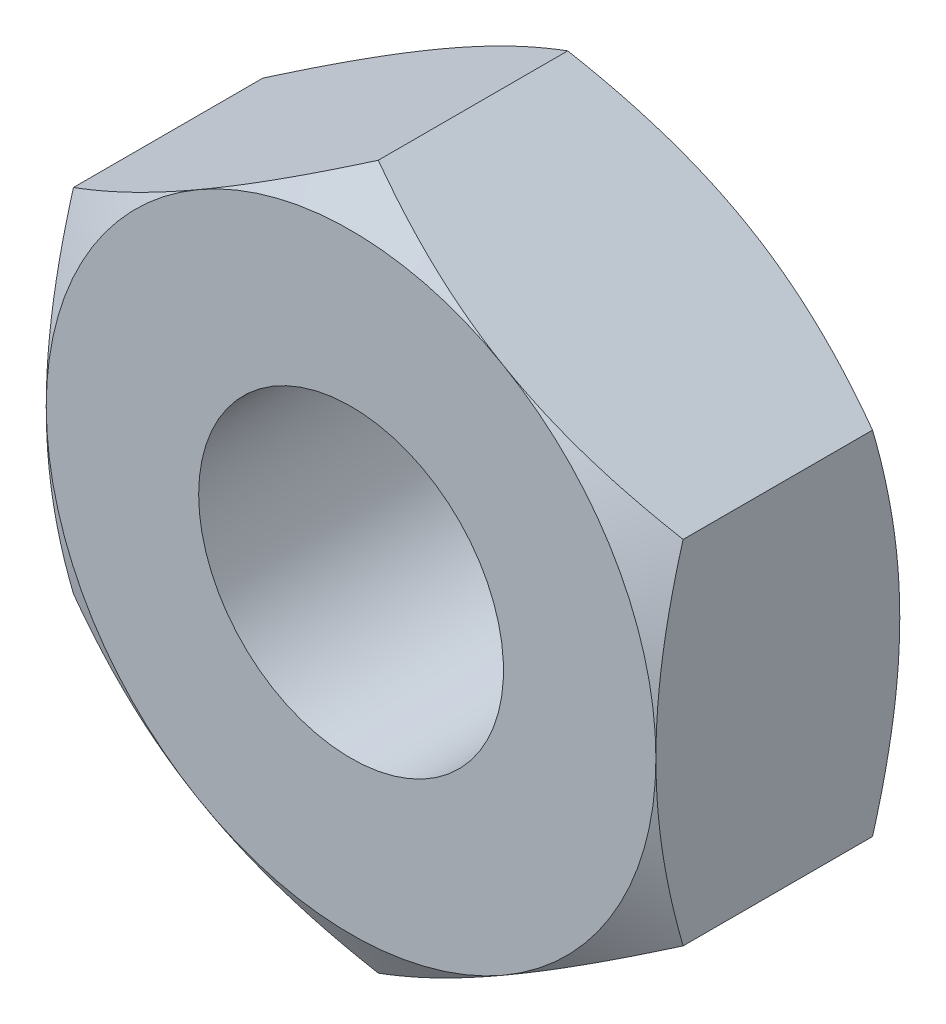
SolidWorks part; units mm, degrees
ref_plane "Front" through (0, 0, 0) normal (0, 0, 1) x (1, 0, 0)
ref_plane "Top" through (0, 0, 0) normal (0, 1, 0) x (1, 0, 0)
ref_plane "Right" through (0, 0, 0) normal (1, 0, 0) x (0, 0, -1)
sketch "Sketch1" plane through (0, 0, 0) normal (0, 0, 1) x (1, 0, 0)
  line L1 (-2.5, 1.4434) -> (-2.5, -1.4434)
  line L2 (-2.5, -1.4434) -> (0, -2.8868)
  line L3 (0, -2.8868) -> (2.5, -1.4434)
  line L4 (2.5, -1.4434) -> (2.5, 1.4434)
  line L5 (2.5, 1.4434) -> (0, 2.8868)
  line L6 (0, 2.8868) -> (-2.5, 1.4434)
  circle A0 centre (0, 0) radius 2.5 construction
  circle A1 centre (0, 0) radius 1.25 construction
  point P10 (0, 1.25)
  dimension "hex" = 5
  dimension "dia" = 2.5
extrude "Extrude1" add sketch "Sketch1" along normal mid plane 2
sketch "Sketch4" plane through (0, 0, -1) normal (0, 0, -1) x (-1, 0, 0)
  circle A0 centre (0, 0) radius 1.25 construction
  circle A1 centre (0, 0) radius 1.25
sketch "Sketch10" plane through (0, 0, 1) normal (0, 0, 1) x (1, 0, 0)
  circle A0 centre (0, 0) radius 1.25 construction
  circle A1 centre (0, 0) radius 1.25
extrude "Cut-Extrude2" cut sketch "Sketch10" against normal through all draft 45
sketch "Sketch11" plane through (0, 0, -1) normal (0, 0, -1) x (-1, 0, 0)
  circle A0 centre (0, 0) radius 1.25 construction
  circle A1 centre (0, 0) radius 1.25
extrude "Cut-Extrude3" cut sketch "Sketch11" against normal through all draft 45
sketch "Sketch13" plane through (0, 0, -1) normal (0, 0, -1) x (-1, 0, 0)
  circle A0 centre (0, 0) radius 1.25 construction
  circle A1 centre (0, 0) radius 1.25
extrude "Boss-Extrude1" add sketch "Sketch13" against normal up to vertex (2 mm away) separate body up to point (-2.5, 1.4434, 1)
curve "Helix/Spiral3" [suppressed] pitch 0.45 height 2 turns 4.4444
sketch "Sketch12" plane through (0, 0, 0) normal (1, 0, 0) x (0, 0, -1)
  line L0 (1.3938, 1.25) -> (1, 1.25)
  line L1 (1.3938, 1.25) -> (1.225, 0.9577)
  line L2 (1.225, 0.9577) -> (1.1688, 0.9577)
  line L3 (1.1688, 0.9577) -> (1, 1.25)
  line L4 (1.1969, 0.9577) -> (1.1969, 1.25) construction
  line L5 (1.0844, 1.1039) -> (1.3094, 1.1039) construction
  dimension "D1" = 60
  dimension "D2" = 0.0563
  dimension "D3" = 0.225
sweep "Cut-Sweep1" [suppressed] cut profiles "Sketch12" path "Helix/Spiral3"
combine bodies "Combine1" operation type subtract main body 116 bodies to subtract 117
sketch "Sketch7" plane through (0, 0, 1) normal (0, 0, 1) x (1, 0, 0)
  circle A0 centre (0, 0) radius 2.5 construction
  circle A1 centre (0, 0) radius 2.5
extrude "Extrude2" cut sketch "Sketch7" against normal blind 25.4 draft 60 flip side to cut
mirror "Mirror2" about plane through (0, 0, 0) normal (0, 0, 1) of "Extrude2"
sketch "Sketch8" plane through (0, 0, 1) normal (0, 0, 1) x (1, 0, 0)
  line L0 (-0.8839, 0.8839) -> (0, 0) construction
  line L1 (0, -1.2361) -> (0, 1.2361) construction
  circle A1 centre (0, 0) radius 1.25 construction
  point P0 (-0.8839, 0.8839)
  dimension "D1" = 45
sketch "Sketch14" plane through (0, 0, 1) normal (0, 0, 1) x (1, 0, 0)
  line L0 (0, 0) -> (-1.25, 0) construction
  circle A0 centre (0, 0) radius 1.25 construction
sketch "Sketch15" plane through (0, 0, 0) normal (1, 0, 0) x (0, 0, -1)
  line L0 (1, -1.25) -> (1, 1.25) construction
  line L1 (-1, 1.25) -> (-1, -1.25) construction
  point P0 (-1, 0)
  point P1 (1, 0)
equation "\"D3@Helix/Spiral3\" = \"length@Extrude1\" "
equation "\"D2@Sketch12\" = \"D4@Helix/Spiral3\"*.125"
equation "\"D3@Sketch12\" = \"D4@Helix/Spiral3\"*.50"
